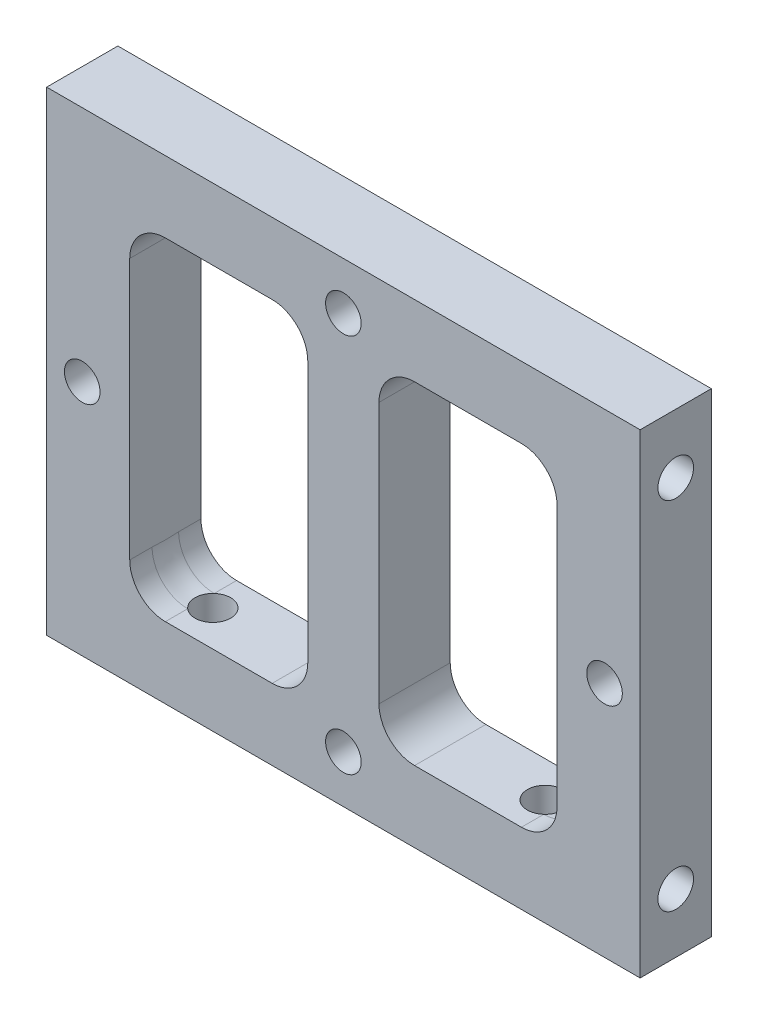
SolidWorks part; units mm, degrees
ref_plane "前视基准面" through (0, 0, 0) normal (0, 0, 1) x (1, 0, 0)
ref_plane "上视基准面" through (0, 0, 0) normal (0, 1, 0) x (1, 0, 0)
ref_plane "右视基准面" through (0, 0, 0) normal (1, 0, 0) x (0, 0, -1)
ref_plane "基准面1" through (0, 0, 3) normal (0, 0, 1) x (1, 0, 0)
sketch "草图1" plane through (0, 0, 3) normal (0, 0, 1) x (1, 0, 0)
  line L0 (-25, 20) -> (-25, -20)
  line L1 (-25, -20) -> (25, -20)
  line L2 (25, -20) -> (25, 20)
  line L3 (25, 20) -> (-25, 20)
extrude "凸台-拉伸1" add sketch "草图1" against normal blind 6
sketch "草图2" plane through (0, 0, 3) normal (0, 0, 1) x (1, 0, 0)
  line L0 (18, 14) -> (3, 14)
  line L1 (3, 14) -> (3, -14)
  line L2 (3, -14) -> (18, -14)
  line L3 (18, -14) -> (18, 14)
extrude "切除-拉伸1" cut sketch "草图2" against normal through all
sketch "草图3" plane through (0, 0, -3) normal (0, 0, -1) x (-1, 0, 0)
  line L0 (3, 14) -> (3, -14)
  line L1 (3, -14) -> (18, -14)
  line L2 (18, -14) -> (18, 14)
  line L3 (18, 14) -> (3, 14)
extrude "切除-拉伸2" cut sketch "草图3" against normal through all
hole_wizard "Ø3.0 (3) 直径孔1" positions "草图5" profile "草图4" hole size "Ø3.0" standard "ANSI Metric"
sketch "草图5" plane through (0, 0, 3) normal (0, 0, 1) x (1, 0, 0)
  point P0 (-22, 0)
  point P1 (0, -16)
  point P2 (22, 0)
  point P3 (0, 16)
sketch "草图4" plane through (-22, 0, 3) normal (1, 0, 0) x (0, -1, 0)
  line L0 (0, 0) -> (0, 6)
  line L1 (0, 6) -> (1.5, 6)
  line L2 (1.5, 6) -> (1.5, 0)
  line L5 (1.5, 0) -> (0, 0)
  line L11 (0, -6.35) -> (0, 107.95) construction
  dimension "通孔孔直径" = 3
  dimension "通孔孔深度" = 6
hole_wizard "Ø3.0 (3) 直径孔2" positions "草图7" profile "草图6" hole size "Ø3.0" standard "ANSI Metric"
sketch "草图7" plane through (25, 0, 0) normal (1, 0, 0) x (0, 0, -1)
  point P0 (0, -15)
  point P1 (0, 15)
sketch "草图6" plane through (25, -15, 0) normal (0, 1, 0) x (0, 0, -1)
  line L0 (0, 0) -> (0, 6)
  line L1 (0, 6) -> (1.5, 6)
  line L2 (1.5, 6) -> (1.5, 0)
  line L5 (1.5, 0) -> (0, 0)
  line L10 (0, 6) -> (-1.5, 6) construction
  line L11 (0, -6.35) -> (0, 107.95) construction
  dimension "孔直径" = 3
  dimension "孔深度" = 6
  dimension "导头角度" = 180
hole_wizard "Ø3.0 (3) 直径孔3" positions "草图9" profile "草图8" hole size "Ø3.0" standard "ANSI Metric"
sketch "草图9" plane through (0, -20, 0) normal (0, -1, 0) x (-1, 0, 0)
  point P0 (14, 0)
  point P1 (-14, 0)
sketch "草图8" plane through (-14, -20, 0) normal (1, 0, 0) x (0, 0, -1)
  line L0 (0, 0) -> (0, 6)
  line L1 (0, 6) -> (1.5, 6)
  line L2 (1.5, 6) -> (1.5, 0)
  line L5 (1.5, 0) -> (0, 0)
  line L11 (0, -6.35) -> (0, 107.95) construction
  dimension "通孔孔直径" = 3
  dimension "通孔孔深度" = 6
hole_wizard "Ø3.0 (3) 直径孔4" positions "草图11" profile "草图10" hole size "Ø3.0" standard "ANSI Metric"
sketch "草图11" plane through (-25, 0, 0) normal (-1, 0, 0) x (0, 0, 1)
  point P0 (0, -15)
  point P1 (0, 15)
sketch "草图10" plane through (-25, -15, 0) normal (0, 1, 0) x (0, 0, 1)
  line L0 (0, 0) -> (0, 6)
  line L1 (0, 6) -> (1.5, 6)
  line L2 (1.5, 6) -> (1.5, 0)
  line L5 (1.5, 0) -> (0, 0)
  line L10 (0, 6) -> (-1.5, 6) construction
  line L11 (0, -6.35) -> (0, 107.95) construction
  dimension "孔直径" = 3
  dimension "孔深度" = 6
  dimension "导头角度" = 180
fillet "圆角1" radius 3 8 edges at (3, -14, 0) (18, 14, 0) (3, 14, 0) (-18, -14, 0) (18, -14, 0) (-18, 14, 0) (-3, -14, 0) (-3, 14, 0) tangent propagation no
